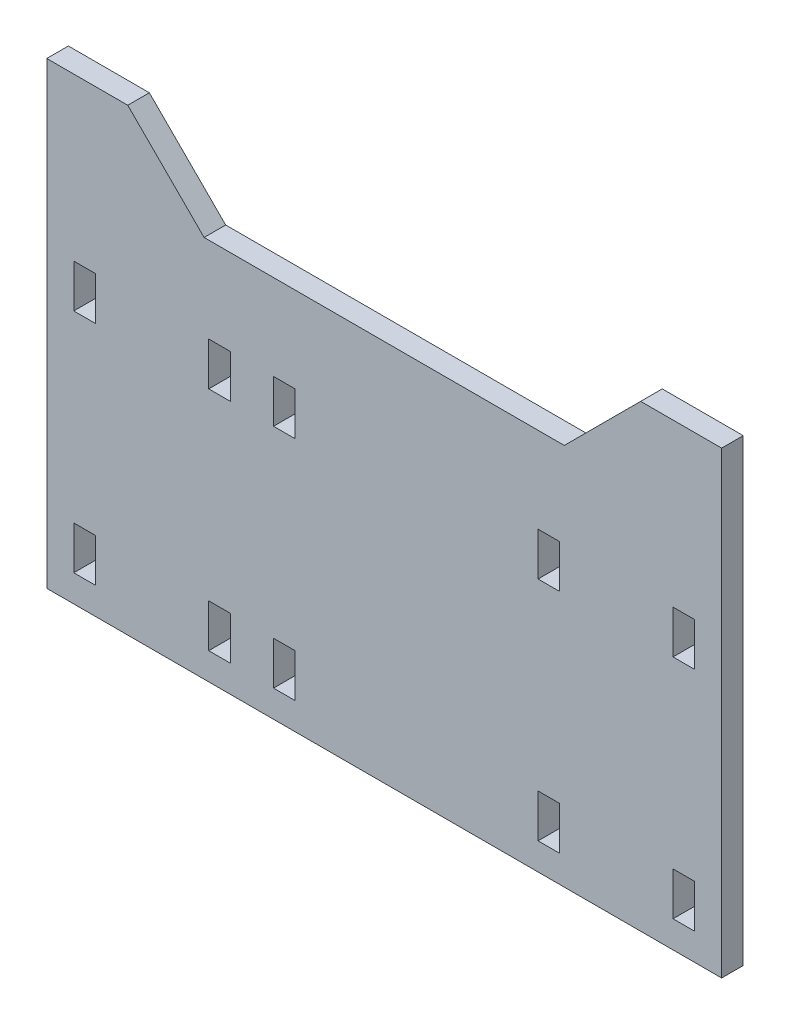
SolidWorks part; units mm, degrees
ref_plane "Front Plane" through (0, 0, 0) normal (0, 0, 1) x (1, 0, 0)
ref_plane "Top Plane" through (0, 0, 0) normal (0, 1, 0) x (1, 0, 0)
ref_plane "Right Plane" through (0, 0, 0) normal (1, 0, 0) x (0, 0, -1)
sketch "Sketch1" plane through (0, 0, 0) normal (0, 0, 1) x (1, 0, 0)
  line L0 (0, 66.0849) -> (0, -70.4198) construction
  line L6 (-38.5, 25) -> (-34.5, 25)
  line L7 (22.5, 25) -> (26.5, 25)
  line L8 (22.5, 25) -> (22.5, 17)
  line L9 (22.5, 17) -> (26.5, 17)
  line L10 (26.5, 25) -> (26.5, 17)
  line L11 (-103.5149, 0) -> (102.2922, 0) construction
  line L12 (22.5, -17) -> (26.5, -17)
  line L13 (22.5, -25) -> (22.5, -17)
  line L14 (26.5, -25) -> (26.5, -17)
  line L15 (22.5, -25) -> (26.5, -25)
  line L16 (-22.5, 25) -> (-26.5, 25)
  line L17 (-22.5, 25) -> (-22.5, 17)
  line L18 (-26.5, 25) -> (-26.5, 17)
  line L19 (-22.5, 17) -> (-26.5, 17)
  line L20 (-22.5, -17) -> (-26.5, -17)
  line L21 (-22.5, -25) -> (-22.5, -17)
  line L22 (-26.5, -25) -> (-26.5, -17)
  line L23 (-22.5, -25) -> (-26.5, -25)
  line L36 (56.5, 30) -> (56.5, -30)
  line L39 (47.5, 25) -> (51.5, 25)
  line L40 (47.5, 25) -> (47.5, 17)
  line L41 (47.5, 17) -> (51.5, 17)
  line L42 (51.5, 25) -> (51.5, 17)
  line L43 (47.5, -17) -> (51.5, -17)
  line L44 (47.5, -17) -> (47.5, -25)
  line L45 (47.5, -25) -> (51.5, -25)
  line L46 (51.5, -17) -> (51.5, -25)
  line L47 (-38.5, 25) -> (-38.5, 17)
  line L48 (-38.5, 17) -> (-34.5, 17)
  line L49 (-34.5, 25) -> (-34.5, 17)
  line L50 (-38.5, -17) -> (-34.5, -17)
  line L51 (-38.5, -17) -> (-38.5, -25)
  line L52 (-38.5, -25) -> (-34.5, -25)
  line L53 (-34.5, -17) -> (-34.5, -25)
  line L57 (-68.5, 30) -> (-68.5, -30)
  line L59 (-68.5, 30) -> (56.5, 30)
  line L60 (-63.5, 25) -> (-59.5, 25)
  line L61 (-63.5, 25) -> (-63.5, 17)
  line L62 (-63.5, 17) -> (-59.5, 17)
  line L63 (-59.5, 25) -> (-59.5, 17)
  line L64 (-63.5, -17) -> (-59.5, -17)
  line L65 (-63.5, -17) -> (-63.5, -25)
  line L66 (-63.5, -25) -> (-59.5, -25)
  line L67 (-59.5, -17) -> (-59.5, -25)
  line L68 (-68.5, -30) -> (56.5, -30)
  point P0 (0, 0)
  dimension "D2" = 60
  dimension "D3" = 8
  dimension "D4" = 125
  dimension "D5" = 4
  dimension "D6" = 8
  dimension "D7" = 45
  dimension "D8" = 21
  dimension "D9" = 21
  dimension "D10" = 5
  dimension "D12" = 5
extrude "Boss-Extrude1" add sketch "Sketch1" along normal blind 4
sketch "Sketch2" plane through (0, 0, 0) normal (0, 0, 1) x (1, 0, 0)
  line L0 (-68.5, 30) -> (-68.5, 55)
  line L1 (-68.5, 55) -> (-53.5, 55)
  line L2 (-53.5, 55) -> (-39.3579, 40.8579)
  line L7 (56.5, 30) -> (-68.5, 30)
  line L8 (41.5, 55) -> (56.5, 55)
  line L9 (56.5, 55) -> (56.5, 30)
  line L10 (41.5, 55) -> (27.3579, 40.8579)
  line L11 (27.3579, 40.8579) -> (-39.3579, 40.8579)
  dimension "D1" = 25
  dimension "D2" = 15
  dimension "D3" = 135
  dimension "D4" = 20
extrude "Boss-Extrude2" add sketch "Sketch2" along normal blind 4
